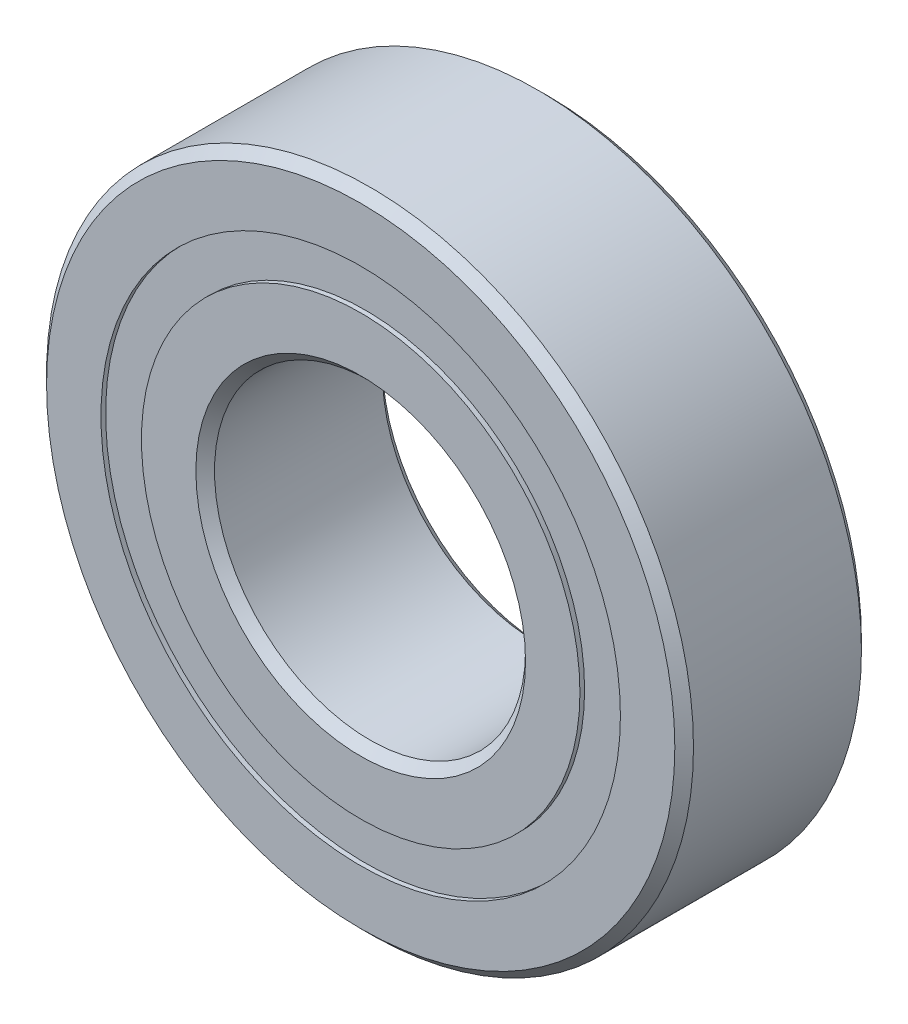
SolidWorks part; units mm, degrees
ref_plane "Front Plane" through (0, 0, 0) normal (0, 0, 1) x (1, 0, 0)
ref_plane "Top Plane" through (0, 0, 0) normal (0, 1, 0) x (1, 0, 0)
ref_plane "Right Plane" through (0, 0, 0) normal (1, 0, 0) x (0, 0, -1)
sketch "Sketch1" plane through (0, 0, 0) normal (1, 0, 0) x (0, 0, -1)
  line L0 (-7.5, 0) -> (7.5, 0) construction
  line L1 (0, 26) -> (0, -26) construction
  line L2 (6.75, 26) -> (-6.75, 26)
  line L3 (-6.75, 26) -> (-7.5, 25.25)
  line L4 (-7.5, 25.25) -> (-7.5, 20.8764)
  line L5 (-7.5, 20.8764) -> (-3.3333, 20.8764)
  line L6 (7.5, 20.8764) -> (3.3333, 20.8764)
  line L7 (7.5, 25.25) -> (7.5, 20.8764)
  line L8 (6.75, 26) -> (7.5, 25.25)
  line L9 (0, 26) -> (0, 19.25) construction
  line L10 (0, 19.25) -> (0, 12.5) construction
  arc A0 (-3.3333, 20.8764) -> (3.3333, 20.8764) centre (0, 19.25) cw
  point P14 (0, 12.5)
  dimension "Width" = 15
  dimension "OD" = 52
  dimension "D1" = 45
  dimension "D2" = 0.75
  dimension "Shaft Dia" = 25
  dimension "D3" = 6.6667
  dimension "D4" = 1.6264
revolve "Revolve1" add sketch "Sketch1" angle 360 about L0
sketch "Sketch3" plane through (0, 0, 0) normal (1, 0, 0) x (0, 0, -1)
  line L0 (-7.5, 17.6236) -> (-3.3333, 17.6236)
  line L1 (0, 26) -> (0, -26) construction
  line L2 (-7.5, 25.25) -> (-7.5, 20.8764) construction
  line L3 (-7.5, 17.6236) -> (-7.5, 13.25)
  line L4 (-6.75, 26) -> (-7.5, 25.25) construction
  line L5 (-7.5, 13.25) -> (-6.75, 12.5)
  line L6 (-6.75, 12.5) -> (6.75, 12.5)
  line L7 (6.75, 26) -> (6.75, -26) construction
  line L8 (6.75, 12.5) -> (7.5, 13.25)
  line L9 (7.5, -25.25) -> (7.5, 25.25) construction
  line L10 (7.5, 13.25) -> (7.5, 17.6236)
  line L11 (7.5, 17.6236) -> (3.3333, 17.6236)
  line L13 (6.75, 26) -> (7.5, 25.25) construction
  arc A0 (3.3333, 20.8764) -> (-3.3333, 20.8764) centre (0, 19.25) ccw construction
  arc A1 (3.3333, 17.6236) -> (-3.3333, 17.6236) centre (0, 19.25) cw
revolve "Revolve3" add sketch "Sketch3" angle 360 about L0
sketch "Sketch4" plane through (0, 0, 0) normal (1, 0, 0) x (0, 0, -1)
  line L0 (-3.7089, 19.25) -> (3.7089, 19.25)
  arc A2 (-3.7089, 19.25) -> (3.7089, 19.25) centre (0, 19.25) cw
  arc A3 (3.3333, 20.8764) -> (-3.3333, 20.8764) centre (0, 19.25) ccw construction
revolve "Revolve4" add sketch "Sketch4" angle 360 about L0
ref_axis "Axis1" through (0, 0, -7.5) along (0, 0, 1)
pattern_circular "CirPattern1" count 12 every 30 about axis through (0, 0, -7.5) along (0, 0, 1) of bodies 104
sketch "Sketch5" plane through (0, 0, 0) normal (1, 0, 0) x (0, 0, -1)
  line L0 (-7.5, 20.8764) -> (-3.3333, 20.8764) construction
  line L1 (-7.125, 20.8764) -> (-3.7089, 20.8764)
  line L2 (-7.125, 20.8764) -> (-7.125, 17.6236)
  line L3 (-7.125, 17.6236) -> (-3.7089, 17.6236)
  line L4 (-3.7089, 20.8764) -> (-3.7089, 17.6236)
  line L5 (-7.5, 17.6236) -> (-3.3333, 17.6236) construction
  line L6 (7.5, 20.8764) -> (3.3333, 20.8764) construction
  line L7 (7.125, 20.8764) -> (3.7089, 20.8764)
  line L8 (7.125, 20.8764) -> (7.125, 17.6236)
  line L9 (7.125, 17.6236) -> (3.7089, 17.6236)
  line L10 (3.7089, 20.8764) -> (3.7089, 17.6236)
  line L11 (7.5, 17.6236) -> (3.3333, 17.6236) construction
  line L12 (-6.75, 26) -> (-7.5, 25.25) construction
  point P18 (-7.125, 25.625)
revolve "Revolve5" add sketch "Sketch5" angle 360 about L0
equation "\"D2@Sketch1\" = \"Width@Sketch1\"*.05"
equation "\"D3@Sketch1\" = \"Width@Sketch1\"/2.25"
equation "\"D4@Sketch1\" = (((\"OD@Sketch1\"-\"Width@Sketch1\")/2)/3.25)/3.5"
equation "\"D2@CirPattern1\" = 360/\"Balls@CirPattern1\""
